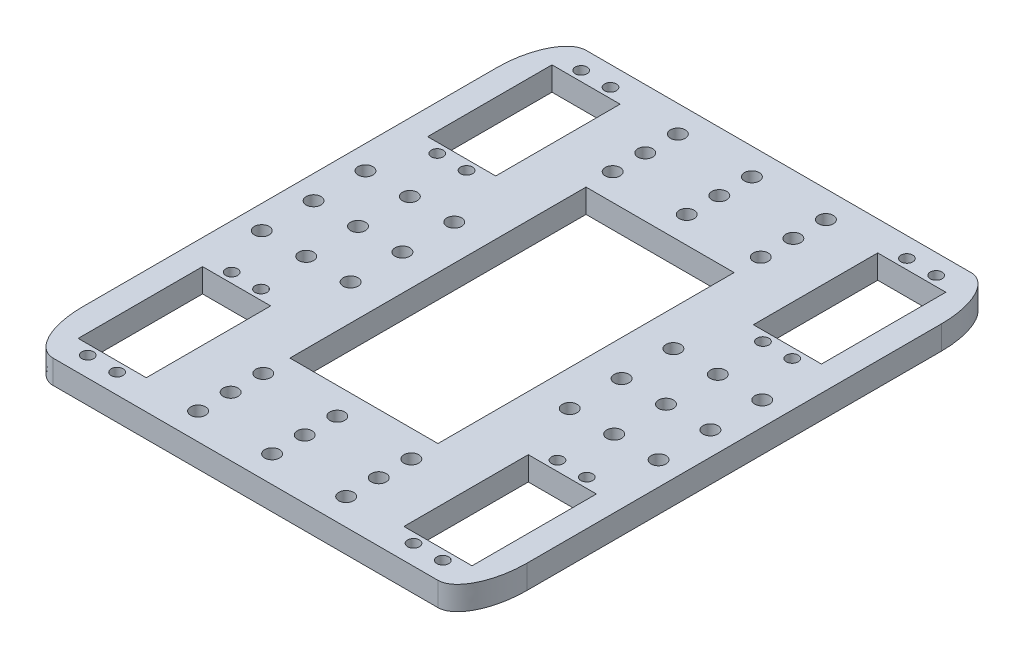
SolidWorks part; units mm, degrees
ref_plane "Front Plane" through (0, 0, 0) normal (0, 0, 1) x (1, 0, 0)
ref_plane "Top Plane" through (0, 0, 0) normal (0, 1, 0) x (1, 0, 0)
ref_plane "Right Plane" through (0, 0, 0) normal (1, 0, 0) x (0, 0, -1)
sketch "Sketch2" plane through (0, 0, 0) normal (0, 1, 0) x (1, 0, 0)
  line L1 (-75, 90) -> (75, 90)
  line L2 (-75, 90) -> (-75, -90)
  line L3 (-75, -90) -> (75, -90)
  line L4 (75, 90) -> (75, -90)
  line L5 (-75, 90) -> (75, -90) construction
  line L6 (-75, -90) -> (75, 90) construction
  point P0 (0, 0)
  dimension "D1" = 150
  dimension "D2" = 180
extrude "Boss-Extrude1" add sketch "Sketch2" along normal mid plane 8
sketch "Sketch3" plane through (0, 4, 0) normal (0, 1, 0) x (1, 0, 0)
  line L0 (-75, 90) -> (-75, -90) construction
  line L9 (-66.5, -38) -> (-43.5, -38)
  line L10 (-66.5, -38) -> (-66.5, -80)
  line L11 (-66.5, -80) -> (-43.5, -80)
  line L12 (-43.5, -38) -> (-43.5, -80)
  line L13 (-75, -90) -> (75, -90) construction
  line L14 (-59.95, -83.3) -> (-50.05, -83.3) construction
  line L15 (-50.05, -83.3) -> (-50.05, -34.7) construction
  circle A0 centre (-59.95, -34.7) radius 2
  circle A1 centre (-50.05, -34.7) radius 2
  circle A2 centre (-59.95, -83.3) radius 2
  circle A3 centre (-50.05, -83.3) radius 2
  point P16 (-50.05, -59)
  point P17 (-43.5, -59)
  point P18 (-55, -83.3)
  point P19 (-55, -80)
  dimension "D5" = 4
  dimension "D1" = 42
  dimension "D2" = 23
  dimension "D3" = 8.5
  dimension "D4" = 10
  dimension "D6" = 48.6
  dimension "D7" = 9.9
extrude "Cut-Extrude1" cut sketch "Sketch3" against normal through all
mirror "Mirror1" about plane through (0, 0, 0) normal (0, 0, 1) of "Cut-Extrude1"
mirror "Mirror2" about plane through (0, 0, 0) normal (1, 0, 0) of "Mirror1"
fillet "Fillet1" radius 10 2 edges at (-75, 0, -90) (75, 0, 90) second distance 20 first distance on face at (0, 0, -90) first distance on face at (0, 0, 90)
fillet "Fillet2" radius 20 2 edges at (75, 0, -90) (-75, 0, 90) second distance 10 first distance on face at (75, 1, 30) first distance on face at (-75, 1, -30)
sketch "Sketch4" plane through (0, 4, 0) normal (0, 1, 0) x (1, 0, 0)
  line L1 (25, -50) -> (-25, -50)
  line L2 (25, -50) -> (25, 50)
  line L3 (25, 50) -> (-25, 50)
  line L4 (-25, -50) -> (-25, 50)
  line L5 (25, -50) -> (-25, 50) construction
  line L6 (25, 50) -> (-25, -50) construction
  point P0 (0, 0)
  dimension "D1" = 50
  dimension "D2" = 100
extrude "Cut-Extrude2" cut sketch "Sketch4" against normal through all
sketch "Sketch5" plane through (0, 4, 0) normal (0, 1, 0) x (1, 0, 0)
  line L0 (65, 90) -> (-65, 90) construction
  line L1 (-25, 81) -> (25, 81) construction
  circle A0 centre (-25, 81) radius 2.5
  circle A1 centre (25, 81) radius 2.5
  circle A2 centre (0, 81) radius 2.5
  circle A3 centre (-25, 70) radius 2.5
  circle A4 centre (0, 70) radius 2.5
  circle A5 centre (25, 70) radius 2.5
  circle A6 centre (-25, 59) radius 2.5
  circle A7 centre (0, 59) radius 2.5
  circle A8 centre (25, 59) radius 2.5
  point P4 (0, 81)
  point P7 (0, 90)
  dimension "D1" = 50
  dimension "D2" = 9
  dimension "D3" = 5
  dimension "D4" = 3
extrude "Cut-Extrude3" cut sketch "Sketch5" against normal through all
sketch "Sketch6" plane through (0, 4, 0) normal (0, 1, 0) x (1, 0, 0)
  line L0 (-67, 17.5) -> (-67, -17.5) construction
  line L1 (-75, 70) -> (-75, -70) construction
  circle A0 centre (-67, 17.5) radius 2.5
  circle A1 centre (-67, -17.5) radius 2.5
  circle A2 centre (-67, 0) radius 2.5
  circle A3 centre (-52, 0) radius 2.5
  circle A4 centre (-52, 17.5) radius 2.5
  circle A5 centre (-52, -17.5) radius 2.5
  circle A6 centre (-37, 0) radius 2.5
  circle A7 centre (-37, 17.5) radius 2.5
  circle A8 centre (-37, -17.5) radius 2.5
  point P4 (-67, 0)
  dimension "D1" = 5
  dimension "D3" = 35
  dimension "D2" = 8
  dimension "D4" = 3
extrude "Cut-Extrude4" cut sketch "Sketch6" against normal through all
mirror "Mirror4" about plane through (0, 0, 0) normal (1, 0, 0) of "Cut-Extrude4"
mirror "Mirror5" about plane through (0, 0, 0) normal (0, 0, 1) of "Cut-Extrude3"
